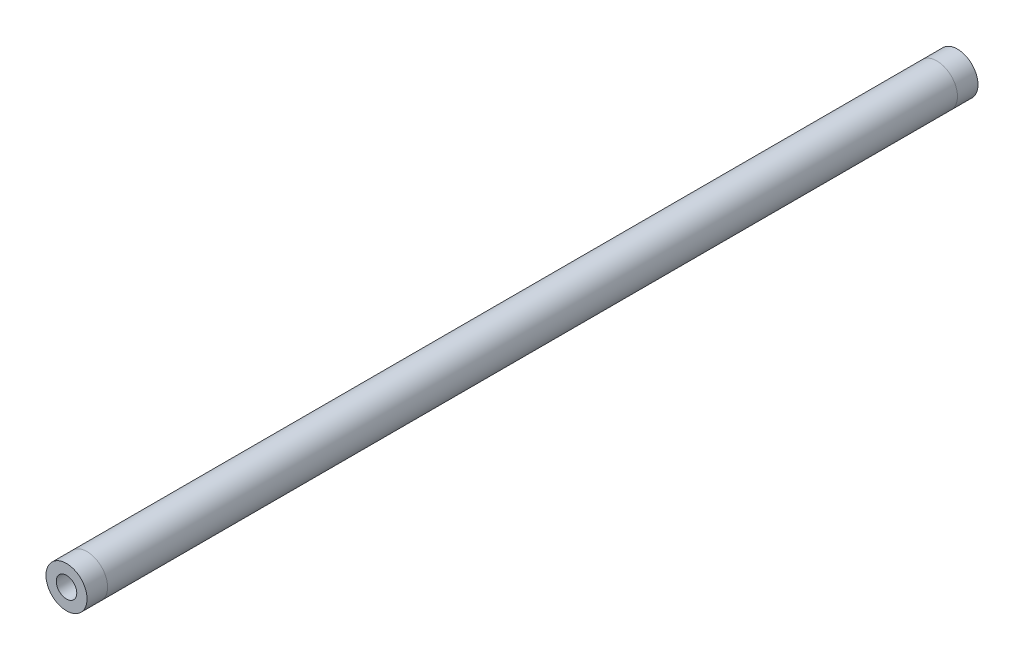
SolidWorks part; units mm, degrees
material "AISI 4130 Steel, annealed at 865C"
ref_plane "Front Plane" through (0, 0, 0) normal (0, 0, 1) x (1, 0, 0)
ref_plane "Top Plane" through (0, 0, 0) normal (0, 1, 0) x (1, 0, 0)
ref_plane "Right Plane" through (0, 0, 0) normal (1, 0, 0) x (0, 0, -1)
sketch "Axis" plane through (0, 0, 0) normal (1, 0, 0) x (0, 0, -1)
  line L0 (0, 0) -> (275.3894, 0) construction
  line L1 (275.3894, 0) -> (269.0394, 0)
  line L2 (275.3894, 0) -> (297.2842, 0) construction
  line L3 (0, 0) -> (-21.8948, 0) construction
  point P4 (0, 0)
  point P5 (275.3894, 0)
  point P6 (269.0394, 0)
  point P8 (297.2842, 0)
  dimension "D1" = 6.35
  dimension "D2" = 21.8948
  dimension "D3" = 21.8948
sketch "Sketch1" plane through (0, 0, 0) normal (0, 0, 1) x (1, 0, 0)
  circle A0 centre (0, 0) radius 6.35
  circle A1 centre (0, 0) radius 4.8514
  circle A2 centre (0, 0) radius 3.175
  dimension "D1" = 12.7
  dimension "D2" = 1.4986
  dimension "D3" = 6.35
extrude "Threaded insert 1-1" add sketch "Sketch1" against normal blind 6.35 contours A0 A1 | A1 A2 region at (-6.1704, 0, 0) region at (-4.7142, 0, 0)
extrude "Threaded insert 1-2" add sketch "Sketch1<3>" against normal blind 9.525 from surface contours A1 A2 region at (-4.7142, 0, 0) starting at face at (6.35, 0, -6.35)
sketch "Sketch1<3>" plane through (0, 0, 0) normal (0, 0, 1) x (1, 0, 0) same geometry as "Sketch1"
extrude "Tube extrude" add sketch "Sketch1<4>" against normal up to vertex (269.0394 mm away) from surface separate body contours A0 A1 region at (-6.1704, 0, 0) up to point (0, 0, -269.0394) starting at face at (4.8514, 0, -6.35)
sketch "Sketch1<4>" plane through (0, 0, 0) normal (0, 0, 1) x (1, 0, 0) same geometry as "Sketch1"
extrude "Threaded insert 2-1" add sketch "Sketch1<6>" along normal blind 9.525 from surface separate body contours A1 A2 region at (-4.7142, 0, 0) starting at face at (4.8514, 0, -269.0394)
sketch "Sketch1<6>" plane through (0, 0, 0) normal (0, 0, 1) x (1, 0, 0) same geometry as "Sketch1"
extrude "Threaded insert 2-2" add sketch "Sketch1<9>" against normal blind 6.35 from surface separate body contours A1 A2 | A0 A1 region at (-6.1704, 0, 0) region at (-4.7142, 0, 0) starting at face at (4.8514, 0, -269.0394)
sketch "Sketch1<9>" plane through (0, 0, 0) normal (0, 0, 1) x (1, 0, 0) same geometry as "Sketch1"
combine bodies "Combine1" operation type add bodies to combine 106 104
equation "\"Threaded insert outer thickness\"= .25"
equation "\"D1@Threaded insert 1-1\"=\"Threaded insert outer thickness\""
equation "\"D1@Threaded insert 2-2\"=\"Threaded insert outer thickness\""
equation "\"D1@Axis\" = \"Threaded insert outer thickness\""
